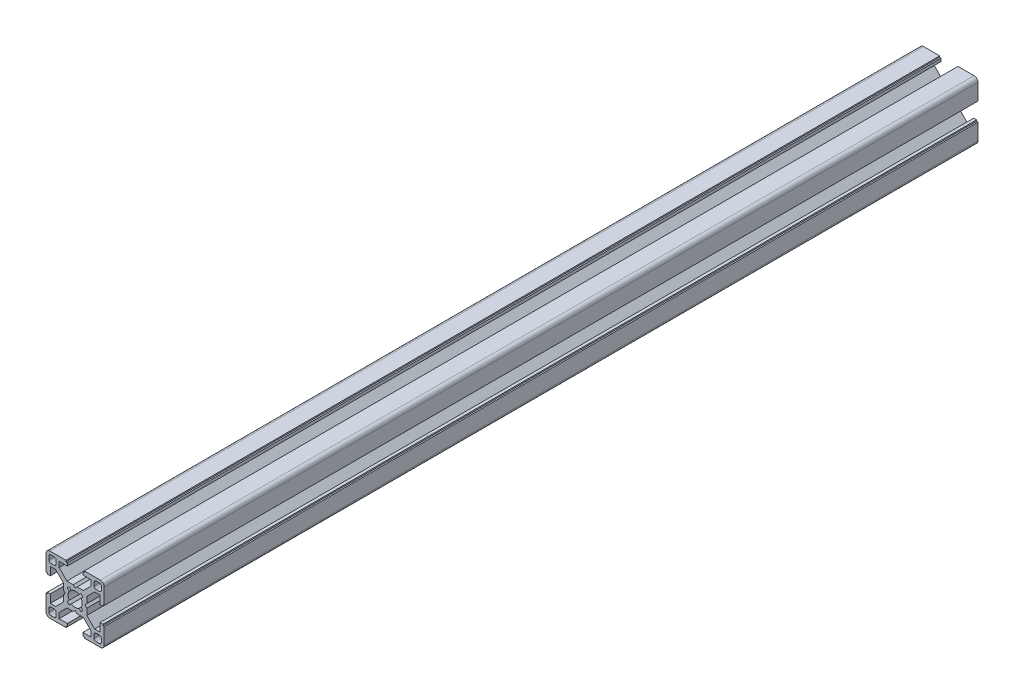
SolidWorks part; units mm, degrees
material "6063-O, Barra estrusa (SS)"
ref_plane "Piano frontale" through (0, 0, 0) normal (0, 0, 1) x (1, 0, 0)
ref_plane "Piano superiore" through (0, 0, 0) normal (0, 1, 0) x (1, 0, 0)
ref_plane "Piano destro" through (0, 0, 0) normal (1, 0, 0) x (0, 0, -1)
sketch "Schizzo1" plane through (0, 0, 0) normal (0, 0, 1) x (1, 0, 0)
  line L0 (-125.0647, 0) -> (53.776, 0) construction
  line L1 (0, -44.8297) -> (0, 95.2781) construction
  line L2 (-15, 13) -> (-15, 4.7)
  line L3 (-15, 4.7) -> (-14.3, 4.7)
  line L4 (-14.3, 4.7) -> (-14.3, 4)
  line L5 (-14.3, 4) -> (-12.8, 4)
  line L6 (-12.8, 4) -> (-12.8, 8.25)
  line L7 (-12.8, 8.25) -> (-10.0178, 8.25)
  line L8 (-10.0178, 8.25) -> (-6, 4.2322)
  line L9 (-6, 4.2322) -> (-6, 1)
  line L10 (-6, 1) -> (-5, 0)
  line L11 (-1, 6) -> (0, 5)
  line L12 (0, 0) -> (-161.3113, 161.3113) construction
  line L13 (-4.2322, 6) -> (-1, 6)
  line L14 (-8.25, 10.0178) -> (-4.2322, 6)
  line L15 (-8.25, 12.8) -> (-8.25, 10.0178)
  line L16 (-4, 12.8) -> (-8.25, 12.8)
  line L17 (-4, 14.3) -> (-4, 12.8)
  line L18 (-4.7, 14.3) -> (-4, 14.3)
  line L19 (-4.7, 15) -> (-4.7, 14.3)
  line L20 (-13, 15) -> (-4.7, 15)
  line L21 (13.5, 10.75) -> (13.5, 12.5)
  line L22 (10.75, 13.5) -> (12.5, 13.5)
  line L23 (9.75, 10.75) -> (9.75, 12.5)
  line L24 (10.75, 9.75) -> (12.5, 9.75)
  line L25 (10.75, -13.5) -> (12.5, -13.5)
  line L26 (13.5, -10.75) -> (13.5, -12.5)
  line L27 (10.75, -9.75) -> (12.5, -9.75)
  line L28 (9.75, -10.75) -> (9.75, -12.5)
  line L29 (-13.5, -10.75) -> (-13.5, -12.5)
  line L30 (-10.75, -13.5) -> (-12.5, -13.5)
  line L31 (-9.75, -10.75) -> (-9.75, -12.5)
  line L32 (-10.75, -9.75) -> (-12.5, -9.75)
  line L33 (1.9955, 3.0562) -> (3.0052, 4.0659)
  line L34 (3.0052, 4.0659) -> (4.0659, 3.0052)
  line L35 (4.0659, 3.0052) -> (3.0562, 1.9955)
  line L36 (3.0562, -1.9955) -> (4.0659, -3.0052)
  line L37 (4.0659, -3.0052) -> (3.0052, -4.0659)
  line L38 (3.0052, -4.0659) -> (1.9955, -3.0562)
  line L39 (-1.9955, -3.0562) -> (-3.0052, -4.0659)
  line L40 (-3.0052, -4.0659) -> (-4.0659, -3.0052)
  line L41 (-4.0659, -3.0052) -> (-3.0562, -1.9955)
  line L42 (1, 6) -> (0, 5)
  line L43 (4.2322, 6) -> (1, 6)
  line L44 (8.25, 10.0178) -> (4.2322, 6)
  line L45 (8.25, 12.8) -> (8.25, 10.0178)
  line L46 (4, 12.8) -> (8.25, 12.8)
  line L47 (12.8, 4) -> (12.8, 8.25)
  line L48 (12.8, 8.25) -> (10.0178, 8.25)
  line L49 (10.0178, 8.25) -> (6, 4.2322)
  line L50 (6, 4.2322) -> (6, 1)
  line L51 (6, 1) -> (5, 0)
  line L52 (6, -1) -> (5, 0)
  line L53 (6, -4.2322) -> (6, -1)
  line L54 (10.0178, -8.25) -> (6, -4.2322)
  line L55 (12.8, -8.25) -> (10.0178, -8.25)
  line L56 (12.8, -4) -> (12.8, -8.25)
  line L57 (4, -12.8) -> (8.25, -12.8)
  line L58 (8.25, -12.8) -> (8.25, -10.0178)
  line L59 (8.25, -10.0178) -> (4.2322, -6)
  line L60 (4.2322, -6) -> (1, -6)
  line L61 (1, -6) -> (0, -5)
  line L62 (-1, -6) -> (0, -5)
  line L63 (-4.2322, -6) -> (-1, -6)
  line L64 (-8.25, -10.0178) -> (-4.2322, -6)
  line L65 (-8.25, -12.8) -> (-8.25, -10.0178)
  line L66 (-4, -12.8) -> (-8.25, -12.8)
  line L67 (-12.8, -4) -> (-12.8, -8.25)
  line L68 (-12.8, -8.25) -> (-10.0178, -8.25)
  line L69 (-10.0178, -8.25) -> (-6, -4.2322)
  line L70 (-6, -4.2322) -> (-6, -1)
  line L71 (-6, -1) -> (-5, 0)
  line L72 (4, 14.3) -> (4, 12.8)
  line L73 (4.7, 14.3) -> (4, 14.3)
  line L74 (4.7, 15) -> (4.7, 14.3)
  line L75 (-3.0562, 1.9955) -> (-4.0659, 3.0052)
  line L76 (-4.0659, 3.0052) -> (-3.0052, 4.0659)
  line L77 (-3.0052, 4.0659) -> (-1.9955, 3.0562)
  line L78 (15, 4.7) -> (14.3, 4.7)
  line L79 (-10.75, 9.75) -> (-12.5, 9.75)
  line L80 (-9.75, 10.75) -> (-9.75, 12.5)
  line L81 (-10.75, 13.5) -> (-12.5, 13.5)
  line L82 (-13.5, 10.75) -> (-13.5, 12.5)
  line L83 (14.3, 4.7) -> (14.3, 4)
  line L84 (14.3, 4) -> (12.8, 4)
  line L85 (14.3, -4) -> (12.8, -4)
  line L86 (14.3, -4.7) -> (14.3, -4)
  line L87 (15, -4.7) -> (14.3, -4.7)
  line L88 (4.7, -15) -> (4.7, -14.3)
  line L89 (4.7, -14.3) -> (4, -14.3)
  line L90 (4, -14.3) -> (4, -12.8)
  line L91 (-4, -14.3) -> (-4, -12.8)
  line L92 (-4.7, -14.3) -> (-4, -14.3)
  line L93 (-4.7, -15) -> (-4.7, -14.3)
  line L94 (-15, -4.7) -> (-14.3, -4.7)
  line L95 (-14.3, -4.7) -> (-14.3, -4)
  line L96 (-14.3, -4) -> (-12.8, -4)
  line L97 (4, 14.3) -> (4, 12.8)
  line L98 (4.7, 14.3) -> (4, 14.3)
  line L99 (4.7, 15) -> (4.7, 14.3)
  line L100 (15, 4.7) -> (14.3, 4.7)
  line L101 (14.3, 4.7) -> (14.3, 4)
  line L102 (14.3, 4) -> (12.8, 4)
  line L103 (13, 15) -> (4.7, 15)
  line L104 (15, 13) -> (15, 4.7)
  line L105 (14.3, -4) -> (12.8, -4)
  line L106 (14.3, -4.7) -> (14.3, -4)
  line L107 (15, -4.7) -> (14.3, -4.7)
  line L108 (4.7, -15) -> (4.7, -14.3)
  line L109 (4.7, -14.3) -> (4, -14.3)
  line L110 (4, -14.3) -> (4, -12.8)
  line L111 (15, -13) -> (15, -4.7)
  line L112 (13, -15) -> (4.7, -15)
  line L113 (-4, -14.3) -> (-4, -12.8)
  line L114 (-4.7, -14.3) -> (-4, -14.3)
  line L115 (-4.7, -15) -> (-4.7, -14.3)
  line L116 (-15, -4.7) -> (-14.3, -4.7)
  line L117 (-14.3, -4.7) -> (-14.3, -4)
  line L118 (-14.3, -4) -> (-12.8, -4)
  line L119 (-13, -15) -> (-4.7, -15)
  line L120 (-15, -13) -> (-15, -4.7)
  arc A0 (-3.65, 0) -> (-3.0562, 1.9955) centre (0, 0) cw
  arc A1 (-1.9955, 3.0562) -> (0, 3.65) centre (0, 0) cw
  arc A2 (-13, 15) -> (-15, 13) centre (-13, 13) ccw
  arc A3 (-13.5, 10.75) -> (-12.5, 9.75) centre (-12.5, 10.75) ccw
  arc A4 (-9.75, 10.75) -> (-10.75, 9.75) centre (-10.75, 10.75) cw
  arc A5 (-10.75, 13.5) -> (-9.75, 12.5) centre (-10.75, 12.5) cw
  arc A6 (-12.5, 13.5) -> (-13.5, 12.5) centre (-12.5, 12.5) ccw
  arc A7 (13.5, 12.5) -> (12.5, 13.5) centre (12.5, 12.5) ccw
  arc A8 (13.5, 10.75) -> (12.5, 9.75) centre (12.5, 10.75) cw
  arc A9 (10.75, 9.75) -> (9.75, 10.75) centre (10.75, 10.75) cw
  arc A10 (10.75, 13.5) -> (9.75, 12.5) centre (10.75, 12.5) ccw
  arc A11 (12.5, -13.5) -> (13.5, -12.5) centre (12.5, -12.5) ccw
  arc A12 (10.75, -13.5) -> (9.75, -12.5) centre (10.75, -12.5) cw
  arc A13 (9.75, -10.75) -> (10.75, -9.75) centre (10.75, -10.75) cw
  arc A14 (13.5, -10.75) -> (12.5, -9.75) centre (12.5, -10.75) ccw
  arc A15 (-13.5, -12.5) -> (-12.5, -13.5) centre (-12.5, -12.5) ccw
  arc A16 (-13.5, -10.75) -> (-12.5, -9.75) centre (-12.5, -10.75) cw
  arc A17 (-10.75, -9.75) -> (-9.75, -10.75) centre (-10.75, -10.75) cw
  arc A18 (-10.75, -13.5) -> (-9.75, -12.5) centre (-10.75, -12.5) ccw
  arc A19 (0, 3.65) -> (1.9955, 3.0562) centre (0, 0) cw
  arc A20 (3.0562, 1.9955) -> (3.65, 0) centre (0, 0) cw
  arc A21 (3.65, 0) -> (3.0562, -1.9955) centre (0, 0) cw
  arc A22 (1.9955, -3.0562) -> (0, -3.65) centre (0, 0) cw
  arc A23 (0, -3.65) -> (-1.9955, -3.0562) centre (0, 0) cw
  arc A24 (-3.0562, -1.9955) -> (-3.65, 0) centre (0, 0) cw
  arc A25 (15, 13) -> (13, 15) centre (13, 13) ccw
  arc A26 (13, -15) -> (15, -13) centre (13, -13) ccw
  arc A27 (-15, -13) -> (-13, -15) centre (-13, -13) ccw
  point P70 (0, 0)
  point P86 (0, 0)
  point P88 (-15, 15)
  point P100 (-9.75, 9.75)
  point P107 (0, 0)
  point P144 (0, 0)
  point P169 (0, 0)
  point P197 (0, 0)
  dimension "D11" = 7.3
  dimension "D14" = 2
  dimension "D17" = 1
  dimension "D1" = 45
  dimension "D2" = 8
  dimension "D3" = 16.5
  dimension "D4" = 9
  dimension "D5" = 2.2
  dimension "D6" = 15
  dimension "D7" = 2.5
  dimension "D8" = 8.3
  dimension "D9" = 2
  dimension "D12" = 5
  dimension "D13" = 1.5
  dimension "D15" = 1.5
  dimension "D16" = 1.5
  dimension "D10" = 4
  dimension "D18" = 4
  dimension "D19" = 4
  dimension "D20" = 4
  dimension "D21" = 4
extrude "Estrusione-Estrusione2" add sketch "Schizzo1" along normal blind 450 contours L120 A27 L119 L93 L92 L91 L66 L65 L64 L63 L62 L61 L60 L59 L58 L57 L90 L89 L88 L112 A26 L111 L87 L86 L85 L56 L55 L54 L53 L52 L51 L50 L49 L48 L47 L84 L83 L78 L104 A25 L103 L74 L73 L72 L46 L45 L44 L43 L42 L11 L13 region at (-14.1142, 14.1142, 0)
